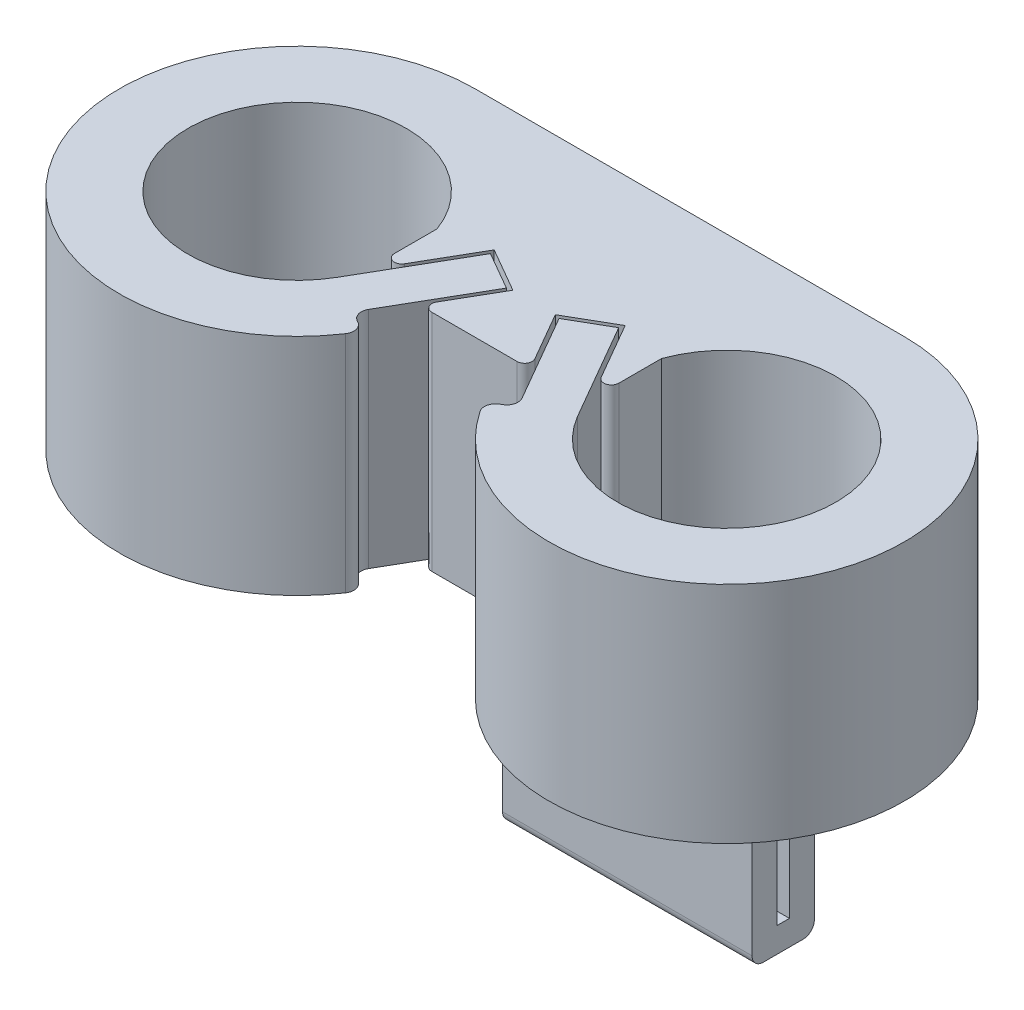
SolidWorks part; units mm, degrees
ref_plane "Front Plane" through (0, 0, 0) normal (0, 0, 1) x (1, 0, 0)
ref_plane "Top Plane" through (0, 0, 0) normal (0, 1, 0) x (1, 0, 0)
ref_plane "Right Plane" through (0, 0, 0) normal (1, 0, 0) x (0, 0, -1)
sketch "Sketch1" plane through (0, 0, 0) normal (0, 1, 0) x (1, 0, 0)
  line L1 (-9, 3) -> (9, 3)
  line L2 (-9, 3) -> (-9, -3)
  line L3 (-9, -3) -> (9, -3)
  line L4 (9, 3) -> (9, -3)
  line L5 (-9, 3) -> (9, -3) construction
  line L6 (-9, -3) -> (9, 3) construction
  point P4 (0, 0)
  dimension "D1" = 6
  dimension "D2" = 18
extrude "Boss-Extrude1" add sketch "Sketch1" along normal blind 18
sketch "Sketch2" plane through (0, 18, 0) normal (0, 1, 0) x (1, 0, 0)
  line L0 (-17.2196, 0) -> (0, 0) construction
  line L1 (0, 0) -> (0, 3) construction
  line L2 (9, 3) -> (-9, 3) construction
  line L3 (-9, 3) -> (-5.3427, 3)
  line L4 (-9.6419, -4.375) -> (-6.6108, -6.125)
  line L5 (-17.2196, 0) -> (-9.6419, -4.375) construction
  line L6 (17.2196, 0) -> (9.6419, -4.375) construction
  line L7 (9.6419, -4.375) -> (6.6108, -6.125)
  line L8 (9, 3) -> (5.3427, 3)
  arc A0 (-9, 3) -> (-9.6419, -4.375) centre (-17.2196, 0) ccw
  arc A2 (-5.3427, 3) -> (-6.6108, -6.125) centre (-17.2196, 0) ccw
  arc A4 (-6.6108, -6.125) -> (-4.9696, 0) centre (-17.2196, 0) ccw construction
  arc A5 (-9.6419, -4.375) -> (-8.4696, 0) centre (-17.2196, 0) ccw construction
  arc A6 (-8.4696, 0) -> (-9, 3) centre (-17.2196, 0) ccw construction
  arc A7 (-4.9696, 0) -> (-5.3427, 3) centre (-17.2196, 0) ccw construction
  arc A8 (4.9696, 0) -> (5.3427, 3) centre (17.2196, 0) cw construction
  arc A9 (8.4696, 0) -> (9, 3) centre (17.2196, 0) cw construction
  arc A10 (9.6419, -4.375) -> (8.4696, 0) centre (17.2196, 0) cw construction
  arc A11 (6.6108, -6.125) -> (4.9696, 0) centre (17.2196, 0) cw construction
  arc A12 (5.3427, 3) -> (6.6108, -6.125) centre (17.2196, 0) cw
  arc A13 (9, 3) -> (9.6419, -4.375) centre (17.2196, 0) cw
  dimension "D1" = 17.5
  dimension "D2" = 3.5
  dimension "D3" = 30
extrude "Boss-Extrude2" add sketch "Sketch2" against normal up to surface (18 mm away) up to face at (0, 0, 0)
sketch "Sketch3" plane through (0, 18, 0) normal (0, 1, 0) x (1, 0, 0)
  line L0 (-17.2196, 12.25) -> (17.2196, 12.25)
  line L1 (-5.3427, 3) -> (5.3427, 3)
  arc A0 (-5.3427, 3) -> (-6.6108, -6.125) centre (-17.2196, 0) ccw construction
  arc A1 (6.6108, -6.125) -> (5.3427, 3) centre (17.2196, 0) ccw construction
  arc A2 (-5.3427, 3) -> (-17.2196, 12.25) centre (-17.2196, 0) ccw
  arc A3 (5.3427, 3) -> (17.2196, 12.25) centre (17.2196, 0) cw
  arc A4 (6.6108, -6.125) -> (5.3427, 3) centre (17.2196, 0) ccw construction
extrude "Boss-Extrude3" add sketch "Sketch3" against normal up to surface (18 mm away) up to face at (0, 0, 0.561)
sketch "Sketch8" plane through (0, 0, 0) normal (0, -1, 0) x (1, 0, 0)
  line L0 (9.6419, 4.375) -> (5.1419, -3.4192) construction
  line L1 (5.1419, -3.4192) -> (2.1108, -1.6692) construction
  line L2 (2.1108, -1.6692) -> (6.6108, 6.125) construction
  line L3 (6.6108, 6.125) -> (9.6419, 4.375) construction
  line L4 (9, 2.6632) -> (5.2517, -3.829)
  line L5 (9, 3) -> (9, -3) construction
  line L6 (5.2517, -3.829) -> (1.701, -1.779)
  line L7 (1.701, -1.779) -> (4.4602, 3)
  line L8 (-9, 3) -> (9, 3) construction
  line L9 (0, -18.0645) -> (0, 0) construction
  line L10 (4.4602, 3) -> (9, 3)
  line L11 (9, 3) -> (9, 2.6632)
  line L12 (-4.4602, 3) -> (-9, 3)
  line L13 (-1.701, -1.779) -> (-4.4602, 3)
  line L14 (-5.2517, -3.829) -> (-1.701, -1.779)
  line L15 (-9, 2.6632) -> (-5.2517, -3.829)
  line L16 (-9, 3) -> (-9, 2.6632)
  dimension "D1" = 9
  dimension "D2" = 0.3
  dimension "D3" = 0.3
  dimension "D4" = 0.3
extrude "Cut-Extrude1" cut sketch "Sketch8" against normal through all
sketch "Sketch5" plane through (0, 18, 0) normal (0, 1, 0) x (1, 0, 0)
  line L0 (17.2196, 12.25) -> (-17.2196, 12.25) construction
  line L1 (-10, 12.25) -> (10, 12.25)
  line L2 (-10, 12.25) -> (-10, 14.25)
  line L3 (-10, 14.25) -> (10, 14.25)
  line L4 (10, 12.25) -> (10, 14.25)
  line L5 (-10, 12.25) -> (10, 14.25) construction
  line L6 (-10, 14.25) -> (10, 12.25) construction
  point P4 (0, 13.25)
  point P7 (0, 0)
  dimension "D1" = 2
  dimension "D2" = 20
extrude "Boss-Extrude4" add sketch "Sketch5" against normal blind 45
sketch "Sketch6" plane through (-10, 0, 0) normal (-1, 0, 0) x (0, 0, 1)
  line L0 (-12.25, 0) -> (12.25, 0) construction
  line L1 (-12.25, -27) -> (-11.25, -27)
  line L2 (-12.25, -27) -> (-12.25, -25)
  line L3 (-12.25, -25) -> (-11.25, -25)
  line L4 (-11.25, -27) -> (-11.25, -25)
  line L5 (-12.25, -27) -> (-11.25, -25) construction
  line L6 (-12.25, -25) -> (-11.25, -27) construction
  line L7 (-11.25, -27) -> (-9.25, -27)
  line L8 (-11.25, -27) -> (-11.25, -1)
  line L9 (-11.25, -1) -> (-9.25, -1)
  line L10 (-9.25, -27) -> (-9.25, -1)
  line L11 (-11.25, -27) -> (-9.25, -1) construction
  line L12 (-11.25, -1) -> (-9.25, -27) construction
  point P4 (-11.75, -26)
  point P9 (-10.25, -14)
  line M12 (-12.25, -27) -> (-12.25, 0)
  dimension "D1" = 2
  dimension "D2" = 1
  dimension "D3" = 1
  dimension "D4" = 2
extrude "Boss-Extrude5" add sketch "Sketch6" against normal up to surface (20 mm away) contours L1 L4 L3 M12 | L7 L10 L9 L8 L4 region at (-10, -26, -11.75) region at (-10, -14, -10.25) up to face at (10, -3.6, -13.05)
sketch "Sketch7" plane through (0, 18, 0) normal (0, 1, 0) x (1, 0, 0)
  line L0 (10, 14.25) -> (17.2196, 14.25)
  line L1 (10, 14.25) -> (-10, 14.25) construction
  line L2 (10, 12.25) -> (17.2196, 12.25)
  line L3 (10, 14.25) -> (10, 12.25)
  line L4 (6.6108, -6.125) -> (4.8788, -7.125)
  line L5 (9.6419, -4.375) -> (6.6108, -6.125) construction
  line L6 (0, 0) -> (0, 14.25) construction
  line L7 (-6.6108, -6.125) -> (-4.8788, -7.125)
  line L8 (-10, 14.25) -> (-17.2196, 14.25)
  line L9 (-10, 14.25) -> (-10, 12.25)
  line L10 (-10, 12.25) -> (-17.2196, 12.25)
  arc A0 (4.8788, -7.125) -> (17.2196, 14.25) centre (17.2196, 0) ccw
  arc A1 (6.6108, -6.125) -> (17.2196, 12.25) centre (17.2196, 0) ccw
  arc A2 (6.6108, -6.125) -> (17.2196, 12.25) centre (17.2196, 0) ccw construction
  arc A3 (10, 12.2857) -> (4.8788, -7.125) centre (17.2196, 0) ccw construction
  arc A4 (17.2196, 14.25) -> (10, 12.2857) centre (17.2196, 0) ccw construction
  arc A5 (17.2196, 12.25) -> (6.6108, -6.125) centre (17.2196, 0) ccw construction
  arc A6 (-4.8788, -7.125) -> (-17.2196, 14.25) centre (-17.2196, 0) cw
  arc A7 (-6.6108, -6.125) -> (-17.2196, 12.25) centre (-17.2196, 0) cw
sketch "Sketch9" plane through (0, 0, 0) normal (0, -1, 0) x (1, 0, 0)
  line L0 (9.6419, 4.375) -> (5.1419, -3.4192)
  line L1 (5.1419, -3.4192) -> (2.1108, -1.6692)
  line L2 (2.1108, -1.6692) -> (6.6108, 6.125)
  line L3 (0, 0) -> (0, -19.6034) construction
  line L4 (6.6108, 6.125) -> (9.6419, 4.375) construction
  line L5 (1.701, -1.779) -> (5.2517, -3.829) construction
  line L6 (9.6419, 4.375) -> (6.6108, 6.125)
  line L7 (-9.6419, 4.375) -> (-5.1419, -3.4192)
  line L8 (-5.1419, -3.4192) -> (-2.1108, -1.6692)
  line L9 (-2.1108, -1.6692) -> (-6.6108, 6.125)
  line L10 (-9.6419, 4.375) -> (-6.6108, 6.125)
  line M11 (6.6108, 6.125) -> (9.6419, 4.375)
  line M23 (-9.6419, 4.375) -> (-6.6108, 6.125)
  dimension "D1" = 0.3
extrude "Boss-Extrude6" add sketch "Sketch9" against normal up to surface (18 mm away) contours L2 L1 L0 M11 | L8 L9 L7 M23 region at (5.8764, 0, 1.3529) region at (-5.8764, 0, 1.3529) up to face at (0, 18, -2.3454)
fillet "Fillet1" radius 0.6 4 edges at (-9, 9, 2.6632) (-4.4602, 9, 3) (4.4602, 9, 3) (9, 9, 2.6632)
extrude "Boss-Extrude7" add sketch "Sketch7" against normal up to surface (18 mm away) up to face at (0, 0, -1.0098)
fillet "Fillet2" radius 0.9 8 edges at (0, -27, -14.25) (0, -27, -9.25) (-10, 0, -13.25) (10, 0, -13.25) (4.8788, 9, 7.125) (-4.8788, 9, 7.125) (-6.6108, 9, 6.125) (6.6108, 9, 6.125)
